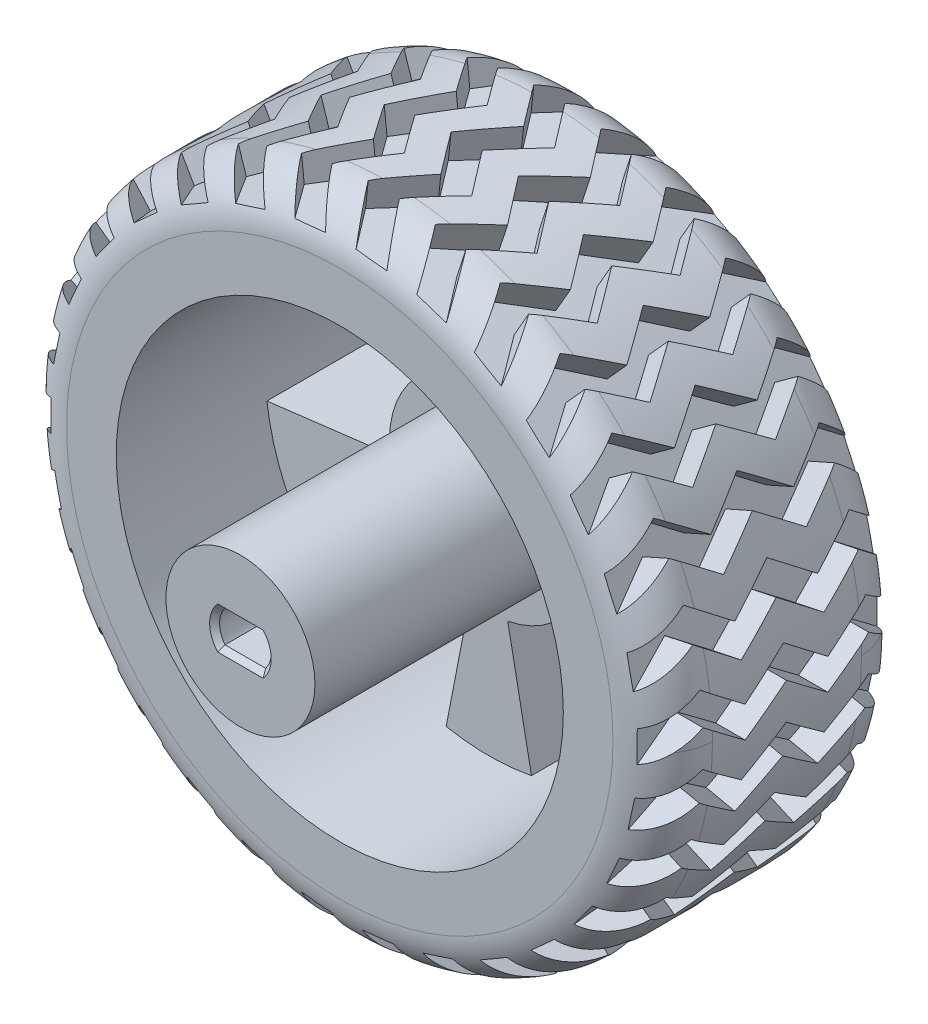
SolidWorks part; units mm, degrees
ref_plane "Plan de face" through (0, 0, 0) normal (0, 0, 1) x (1, 0, 0)
ref_plane "Plan de dessus" through (0, 0, 0) normal (0, 1, 0) x (1, 0, 0)
ref_plane "Plan de droite" through (0, 0, 0) normal (1, 0, 0) x (0, 0, -1)
sketch "Esquisse1" plane through (0, 0, 0) normal (0, 0, 1) x (1, 0, 0)
  circle A0 centre (0, 0) radius 32.5
  dimension "D1" = 65
extrude "Boss.-Extru.1" add sketch "Esquisse1" along normal blind 25
shell "Coque1" thickness 10 removed face at (32.5, 0, 25)
sketch "Esquisse2" plane through (0, 0, 10) normal (0, 0, 1) x (1, 0, 0)
  circle A0 centre (0, 0) radius 7.5
  dimension "D1" = 15
extrude "Boss.-Extru.2" add sketch "Esquisse2" along normal blind 25
fillet "Congé1" radius 5 2 edges at (32.5, 0, 0) (32.5, 0, 25)
sketch "Esquisse4" plane through (0, 0, 10) normal (0, 0, 1) x (1, 0, 0)
  line L0 (-9.5089, 20.3919) -> (-4.2262, 9.0631)
  line L1 (9.5089, 20.3919) -> (4.2262, 9.0631)
  line L2 (22.3323, -2.7421) -> (9.9255, -1.2187)
  line L3 (16.4555, 15.345) -> (7.3135, 6.82)
  line L4 (4.2932, -22.0866) -> (1.9081, -9.8163)
  line L5 (19.6789, -10.9082) -> (8.7462, -4.8481)
  line L6 (-19.6789, -10.9082) -> (-8.7462, -4.8481)
  line L7 (-4.2932, -22.0866) -> (-1.9081, -9.8163)
  line L8 (-16.4555, 15.345) -> (-7.3135, 6.82)
  line L9 (-22.3323, -2.7421) -> (-9.9255, -1.2187)
  arc A0 (-9.5089, 20.3919) -> (9.5089, 20.3919) centre (0, 0) cw
  arc A1 (-4.2262, 9.0631) -> (4.2262, 9.0631) centre (0, 0) cw
  arc A2 (7.3135, 6.82) -> (9.9255, -1.2187) centre (0, 0) cw
  arc A3 (16.4555, 15.345) -> (22.3323, -2.7421) centre (0, 0) cw
  arc A4 (8.7462, -4.8481) -> (1.9081, -9.8163) centre (0, 0) cw
  arc A5 (19.6789, -10.9082) -> (4.2932, -22.0866) centre (0, 0) cw
  arc A6 (-1.9081, -9.8163) -> (-8.7462, -4.8481) centre (0, 0) cw
  arc A7 (-4.2932, -22.0866) -> (-19.6789, -10.9082) centre (0, 0) cw
  arc A8 (-9.9255, -1.2187) -> (-7.3135, 6.82) centre (0, 0) cw
  arc A9 (-22.3323, -2.7421) -> (-16.4555, 15.345) centre (0, 0) cw
  circle A10 centre (0, 0) radius 22.5 construction
  point P7 (0, 22.5)
  point P22 (0, 0)
  dimension "D2" = 10
  dimension "D3" = 50
  dimension "D4" = 5
extrude "Enlèv. mat.-Extru.1" cut sketch "Esquisse4" against normal through all
ref_plane "Plan1" through (32.5, 0, 0) normal (1, 0, 0) x (0, 0, -1)
sketch "Esquisse5" plane through (32.5, 0, 0) normal (1, 0, 0) x (0, 0, -1)
  line L2 (0, -27.5) -> (0, 27.5) construction
  line L7 (0, 1.5625) -> (-4.1667, 4.6875)
  line L10 (-4.1667, 4.6875) -> (-8.3333, 1.5625)
  line L11 (-8.3333, 1.5625) -> (-12.5, 4.6875)
  line L12 (-12.5, 4.6875) -> (-16.6667, 1.5625)
  line L13 (-16.6667, 1.5625) -> (-20.8333, 4.6875)
  line L14 (-20.8333, 4.6875) -> (-25, 1.5625)
  line L15 (-25, 27.5) -> (-25, -27.5) construction
  line L16 (0, -1.5625) -> (-4.1667, 1.5625)
  line L17 (-4.1667, 1.5625) -> (-8.3333, -1.5625)
  line L18 (-8.3333, -1.5625) -> (-12.5, 1.5625)
  line L19 (-12.5, 1.5625) -> (-16.6667, -1.5625)
  line L20 (-16.6667, -1.5625) -> (-20.8333, 1.5625)
  line L21 (-20.8333, 1.5625) -> (-25, -1.5625)
  line L22 (-25, 1.5625) -> (-25, -1.5625)
  line L23 (0, 1.5625) -> (0, -1.5625)
  point P3 (0, 1.8228)
  point P18 (-4.1667, 4.6322)
  point P19 (-4.1667, 1.5521)
  point P20 (0, 0)
  dimension "D1" = 2
  dimension "D2" = 2.5
extrude "Enlèv. mat.-Extru.2" cut sketch "Esquisse5" against normal blind 3
pattern_circular "Répétition circulaire1" count 30 over 360 about axis through (0, 0, 0) along (0, 0, -1) of "Enlèv. mat.-Extru.2"
sketch "Esquisse6" plane through (0, 0, 35) normal (0, 0, 1) x (1, 0, 0)
  line L0 (-2, 1.5) -> (2, 1.5) construction
  line L1 (-2.0494, 1.6) -> (2.0494, 1.6)
  line L2 (2, -1.5) -> (-2, -1.5) construction
  line L3 (2.0494, -1.6) -> (-2.0494, -1.6)
  arc A0 (-2, 1.5) -> (-2, -1.5) centre (0, 0) ccw construction
  arc A1 (2, -1.5) -> (2, 1.5) centre (0, 0) ccw construction
  arc A2 (2.0494, -1.6) -> (2.0494, 1.6) centre (0, 0) ccw
  arc A3 (-2.0494, 1.6) -> (-2.0494, -1.6) centre (0, 0) ccw
  dimension "D1" = 5
  dimension "D2" = 3
  dimension "D3" = 0.1
extrude "Enlèv. mat.-Extru.3" cut sketch "Esquisse6" against normal blind 7
chamfer "Chanfrein1" distance 0.5 angle 45 4 edges at (0, -1.6, 35) (2.6, 0, 35) (-2.6, 0, 35) (0, 1.6, 35)
